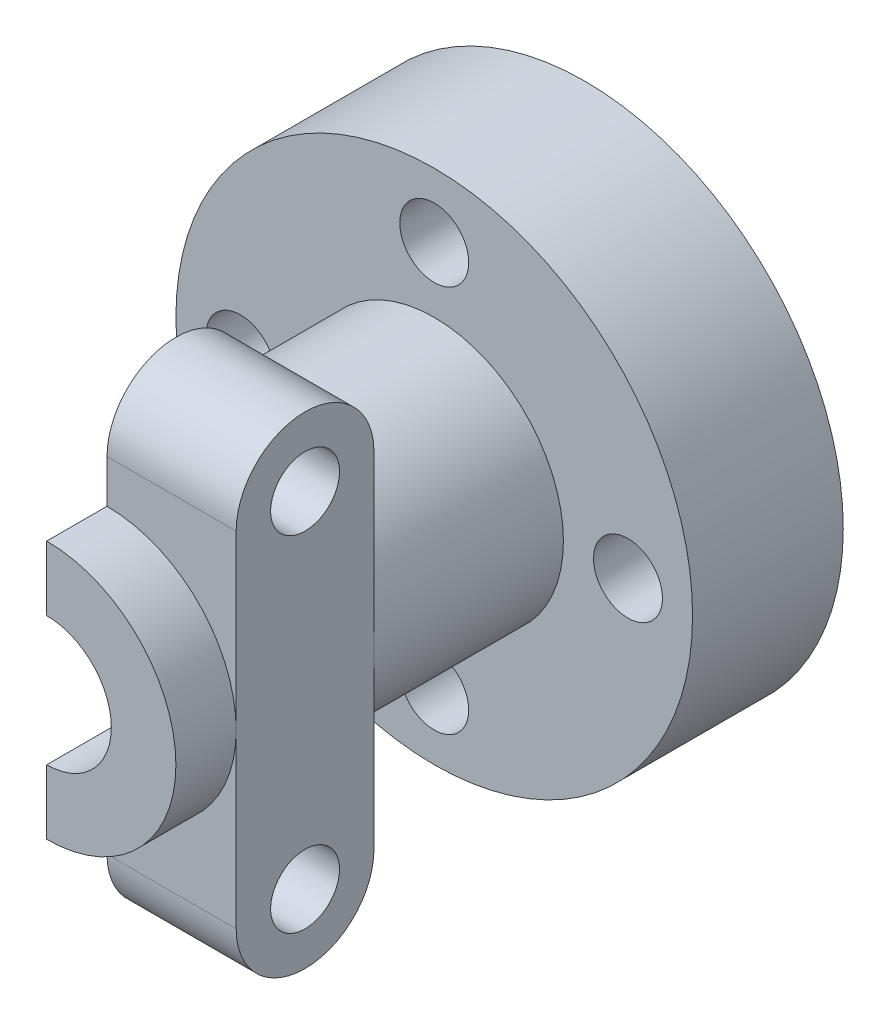
SolidWorks part; units mm, degrees
ref_plane "Front Plane" through (0, 0, 0) normal (1, 0, 0) x (0, 1, 0)
ref_plane "Top Plane" through (0, 0, 0) normal (0, 0, 1) x (0, 1, 0)
ref_plane "Right Plane" through (0, 0, 0) normal (0, 1, 0) x (-1, 0, 0)
sketch "Sketch1" plane through (0, 0, 0) normal (0, 0, 1) x (0, 1, 0)
  circle A0 centre (0, 0) radius 60
  circle A1 centre (0, 0) radius 30
  dimension "D1" = 120
  dimension "D2" = 60
extrude "Boss-Extrude1" add sketch "Sketch1" along normal blind 35 contours A1 | A0 A1 region at (0, -58.3029, 0) region at (0, 0, 0)
extrude "Boss-Extrude2" add sketch "Sketch1<3>" along normal blind 125 contours A1 region at (0, 0, 0)
sketch "Sketch1<3>" plane through (0, 0, 0) normal (0, 0, 1) x (0, 1, 0) same geometry as "Sketch1"
sketch "Sketch4" plane through (0, 0, 0) normal (1, 0, 0) x (0, 1, 0)
  line L0 (40, 95) -> (-40, 95) construction
  line L1 (40, 79) -> (-40, 79)
  line L2 (40, 111) -> (-40, 111)
  line L3 (-60, 0) -> (60, 0) construction
  line L4 (0, 0) -> (0, 22.8363) construction
  arc A0 (40, 79) -> (40, 111) centre (40, 95) ccw
  arc A1 (-40, 111) -> (-40, 79) centre (-40, 95) ccw
  point P2 (0, 95)
  point P12 (0, 0)
  dimension "D2" = 16
  dimension "D1" = 95
  dimension "D3" = 80
extrude "Boss-Extrude3" add sketch "Sketch4" along normal blind 30
sketch "Sketch5" plane through (0, 0, 125) normal (0, 0, 1) x (1, 0, 0)
  circle A0 centre (0, 0) radius 10
  dimension "D1" = 20
extrude "Cut-Extrude2" cut sketch "Sketch5" against normal through all both and the other way through all
sketch "Sketch6" plane through (0, 0, 0) normal (0, 0, 1) x (0, 1, 0)
  line L0 (-30, 0) -> (30, 0)
  arc A0 (-30, 0) -> (30, 0) centre (0, 0) cw
  circle A1 centre (0, 0) radius 30 construction
  circle A2 centre (0, 0) radius 30 construction
sketch "Sketch7" plane through (0, 0, 125) normal (0, 0, 1) x (1, 0, 0)
  line L0 (0, -30) -> (0, 30) construction
  line L1 (0, 30) -> (0, -30)
  arc A0 (0, 30) -> (0, -30) centre (0, 0) ccw
extrude "Cut-Extrude3" cut sketch "Sketch7" against normal blind 60 and the other way through all
sketch "Sketch8" plane through (0, 0, 125) normal (0, 0, 1) x (1, 0, 0)
  line L0 (0, -30) -> (0, 30) construction
  line L1 (0, 15) -> (0, 10)
  line L2 (0, -10) -> (0, -15)
  arc A0 (0, 10) -> (0, -10) centre (0, 0) cw
  arc A1 (0, -10) -> (0, 10) centre (0, 0) ccw construction
  arc A2 (0, 15) -> (0, -15) centre (0, 0) cw
  dimension "D1" = 15
extrude "Cut-Extrude4" cut sketch "Sketch8" against normal up to surface (60 mm away) up to face at (-10, 0, 65)
sketch "Sketch9" plane through (30, 0, 0) normal (1, 0, 0) x (0, 1, 0)
  line L0 (0, 0) -> (0, 51.3912) construction
  circle A0 centre (-40, 95) radius 8
  circle A1 centre (40, 95) radius 8
  dimension "D1" = 16
extrude "Cut-Extrude5" cut sketch "Sketch9" against normal through all
sketch "Sketch10" plane through (0, 0, 35) normal (0, 0, 1) x (1, 0, 0)
  line L0 (-80.3551, 0) -> (82.4467, 0) construction
  line L1 (0, 63.5) -> (0, -66.1837) construction
  circle A0 centre (0, 0) radius 45 construction
  circle A1 centre (-45, 0) radius 8
  circle A2 centre (0, 45) radius 8
  circle A3 centre (45, 0) radius 8
  circle A4 centre (0, -45) radius 8
  point P18 (0, 0)
  dimension "D1" = 90
  dimension "D2" = 16
  dimension "D3" = 4
extrude "Cut-Extrude6" cut sketch "Sketch10" against normal through all
sketch "Sketch11" plane through (0, 0, 0) normal (0, 0, -1) x (1, 0, 0)
  circle A0 centre (0, 0) radius 55
  dimension "D1" = 110
extrude "Cut-Extrude7" cut sketch "Sketch11" against normal blind 15
